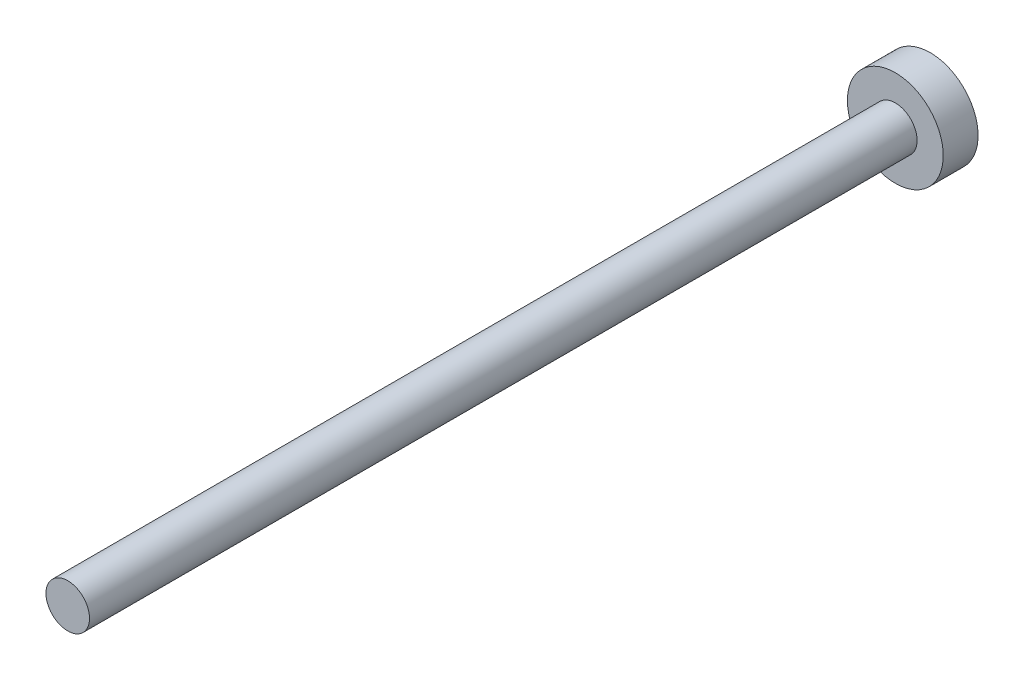
SolidWorks part; units mm, degrees
material "ABS"
ref_plane "Front Plane" through (0, 0, 0) normal (0, 0, 1) x (1, 0, 0)
ref_plane "Top Plane" through (0, 0, 0) normal (0, 1, 0) x (1, 0, 0)
ref_plane "Right Plane" through (0, 0, 0) normal (1, 0, 0) x (0, 0, -1)
sketch "Sketch1" plane through (0, 0, 0) normal (0, 0, 1) x (1, 0, 0)
  circle A0 centre (0, 0) radius 2.5
  dimension "D1" = 5
extrude "Boss-Extrude1" add sketch "Sketch1" along normal mid plane 95
sketch "Sketch2" plane through (0, 0, -47.5) normal (0, 0, -1) x (-1, 0, 0)
  circle A0 centre (0, 0) radius 5.5
  circle A1 centre (0, 0) radius 2.5 construction
  dimension "D1" = 3
extrude "Boss-Extrude2" add sketch "Sketch2" along normal blind 4
